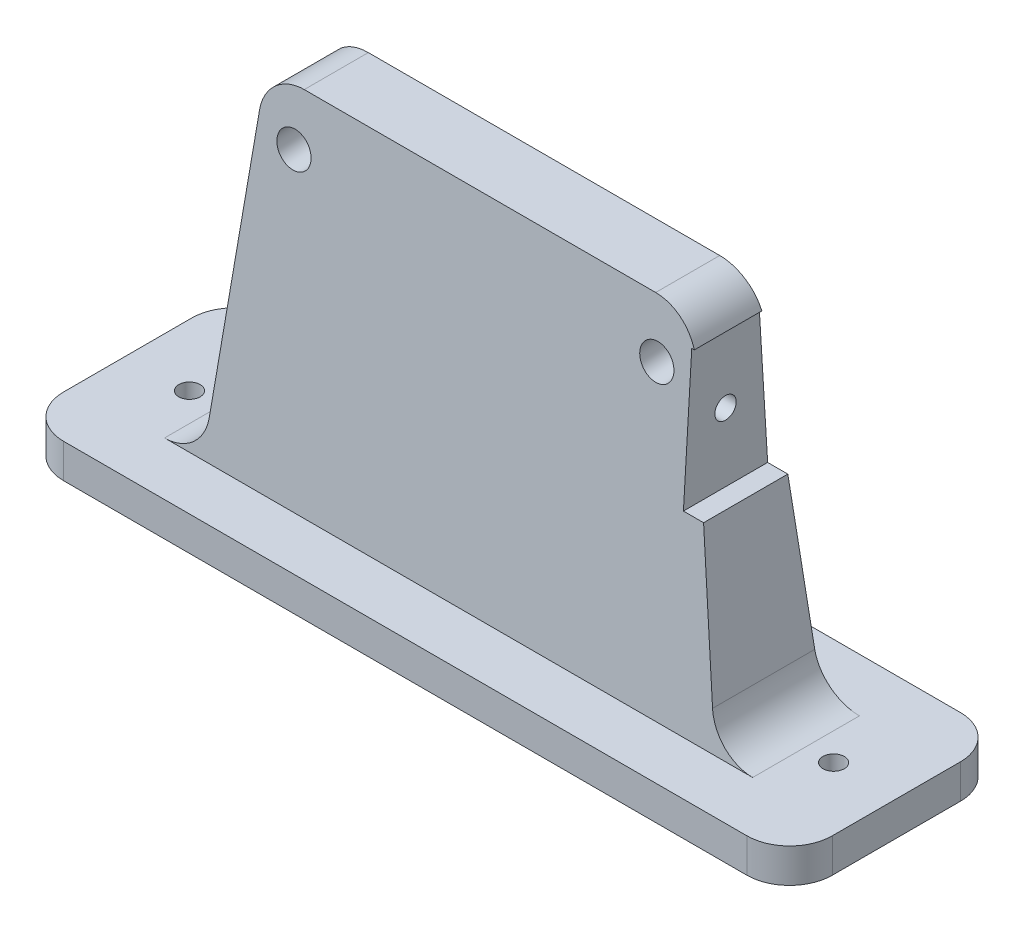
SolidWorks part; units mm, degrees
ref_plane "Front Plane" through (0, 0, 0) normal (0, 0, 1) x (1, 0, 0)
ref_plane "Top Plane" through (0, 0, 0) normal (0, 1, 0) x (1, 0, 0)
ref_plane "Right Plane" through (0, 0, 0) normal (1, 0, 0) x (0, 0, -1)
sketch "Sketch1" plane through (0, 0, 0) normal (0, 1, 0) x (1, 0, 0)
  line L1 (60, 25) -> (-60, 25)
  line L2 (60, 25) -> (60, -25)
  line L3 (60, -25) -> (-60, -25)
  line L4 (-60, 25) -> (-60, -25)
  line L5 (60, 25) -> (-60, -25) construction
  line L6 (60, -25) -> (-60, 25) construction
  point P0 (0, 0)
  dimension "D1" = 120
  dimension "D2" = 50
extrude "Boss-Extrude1" add sketch "Sketch1" along normal blind 8
ref_plane "Plane2" through (0, 90, 0) normal (0, 1, 0) x (1, 0, 0)
sketch "Sketch4" plane through (0, 90, 0) normal (0, 1, 0) x (1, 0, 0)
  line L1 (50, 7.5) -> (-50, 7.5)
  line L2 (50, 7.5) -> (50, -7.5)
  line L3 (50, -7.5) -> (-50, -7.5)
  line L4 (-50, 7.5) -> (-50, -7.5)
  line L5 (50, 7.5) -> (-50, -7.5) construction
  line L6 (50, -7.5) -> (-50, 7.5) construction
  point P0 (0, 0)
  dimension "D1" = 100
  dimension "D2" = 15
sketch "Sketch5" plane through (0, 8, 0) normal (0, 1, 0) x (1, 0, 0)
  line L0 (-60, 25) -> (-60, -25) construction
  line L1 (60, 12.5) -> (-60, 12.5)
  line L2 (60, 12.5) -> (60, -12.5)
  line L3 (60, -12.5) -> (-60, -12.5)
  line L4 (-60, 12.5) -> (-60, -12.5)
  line L5 (60, 12.5) -> (-60, -12.5) construction
  line L6 (60, -12.5) -> (-60, 12.5) construction
  point P0 (0, 0)
  dimension "D1" = 25
loft "Loft1" add profiles "Sketch5", "Sketch4" connector at (-60, 8, 12.5) connector at (-50, 90, 7.5)
sketch "Sketch6" plane through (0, 0.789, -12.9397) normal (0, 0.0609, -0.9981) x (-1, 0, 0)
  line L1 (-60, 7.2244) -> (60, 7.2244) construction
  circle A0 centre (-42.2142, 77.2244) radius 4
  circle A1 centre (42.7841, 77.7677) radius 4
  dimension "D1" = 8
  dimension "D2" = 8
  dimension "D3" = 85
  dimension "D4" = 70
extrude "Cut-Extrude1" cut sketch "Sketch6" against normal blind 82 contours A0
extrude "Cut-Extrude2" cut sketch "Sketch6<4>" against normal blind 82
sketch "Sketch6<4>" plane through (0, 0.789, -12.9397) normal (0, 0.0609, -0.9981) x (-1, 0, 0) same geometry as "Sketch6"
fillet "Fillet4" radius 10 1 edges type face fillet first side face at (0, 90, 0) second side face at (-57.5, 28.5, -5)
fillet "Fillet5" radius 10 1 edges type face fillet first side face at (4.4273, 90, 0) second side face at (57.5, 28.5, 5)
sketch "Sketch13" plane through (-60, 0, 0) normal (-1, 0, 0) x (0, 0, 1)
  line L1 (-25, 8) -> (25, 8)
  line L2 (-25, 8) -> (-25, 0)
  line L3 (-25, 0) -> (25, 0)
  line L4 (25, 8) -> (25, 0)
extrude "Boss-Extrude4" add sketch "Sketch13" along normal blind 30
fillet "Fillet6" radius 10 1 edges at (-90, 4, -25) type face fillet first side face at (-15, 4, -25) second side face at (-90, 4, 0)
fillet "Fillet7" radius 10 1 edges at (-90, 4, 25) type face fillet first side face at (-15, 4, 25) second side face at (-90, 4, 5)
sketch "Sketch14" plane through (60, 0, 0) normal (1, 0, 0) x (0, 0, -1)
  line L1 (-25, 8) -> (25, 8)
  line L2 (-25, 8) -> (-25, 0)
  line L3 (-25, 0) -> (25, 0)
  line L4 (25, 8) -> (25, 0)
extrude "Boss-Extrude5" add sketch "Sketch14" along normal blind 30
fillet "Fillet8" radius 10 1 edges at (90, 4, 25) type face fillet first side face at (90, 4, 0) second side face at (5, 4, 25)
fillet "Fillet9" radius 10 1 edges at (90, 4, -25) type face fillet first side face at (5, 4, -25) second side face at (90, 4, -5)
sketch "Sketch15" plane through (0, 8, 0) normal (0, 1, 0) x (1, 0, 0)
  circle A0 centre (75.3071, 0) radius 2.5
  circle A1 centre (-75.5235, 0) radius 2.5
extrude "Cut-Extrude3" cut sketch "Sketch15" against normal blind 10
sketch "Sketch16" plane through (0, 0, 0) normal (1, 0, 0) x (0, 0, -1)
  circle A0 centre (0, 52.8287) radius 2.5
  dimension "D1" = 5
ref_plane "Plane3" through (40, 0, 0) normal (1, 0, 0) x (0, 0, -1)
sketch "Sketch17" plane through (40, 0, 0) normal (1, 0, 0) x (0, 0, -1)
  line L0 (27.5, 90) -> (-27.5, 90) construction
  circle A0 centre (0, 67.28) radius 2.5
  dimension "D1" = 22.72
extrude "Cut-Extrude4" cut sketch "Sketch17" along normal blind 16 contours A0
sketch "Sketch18" plane through (0, 0.789, 12.9397) normal (0, 0.0609, 0.9981) x (1, 0, 0)
  line L0 (51.0719, 80.5709) -> (51.0719, 52.2775)
  line L1 (51.0719, 52.2775) -> (54.5159, 52.2775)
  line L2 (60, 7.2244) -> (51.0719, 80.5709) construction
  line L3 (54.5159, 52.2775) -> (51.0719, 80.5709)
  point P6 (51.0719, 52.2775)
extrude "Cut-Extrude5" cut sketch "Sketch18" against normal blind 20
sketch "Sketch19" plane through (60.0821, 7.3271, 0) normal (0.9926, 0.1211, 0) x (0, 0, -1)
  line L0 (-8.0359, 74.4308) -> (8.0359, 74.4308)
  line L1 (8.0359, 74.4308) -> (9.8367, 44.6802)
  line L2 (12.5, 0.6779) -> (8.0359, 74.4308) construction
  line L3 (9.8367, 44.6802) -> (-9.758, 45.9807)
  line L4 (-9.758, 45.9807) -> (-8.0359, 74.4308)
  line L5 (9.8367, 44.6802) -> (9.6457, 47.836)
  point P10 (0, 0)
  point P11 (8.0359, 74.4308)
extrude "Cut-Extrude6" cut sketch "Sketch19" along normal blind 1 and the other way blind 1 contours L4 L0 L1 L3
ref_plane "Plane4" through (50, 0, 0) normal (1, 0, 0) x (0, 0, -1)
sketch "Sketch21" plane through (50, 0, 0) normal (1, 0, 0) x (0, 0, -1)
  line L1 (10.3086, 83.28) -> (-10.3086, 83.28)
  line L2 (10.3086, 83.28) -> (10.3086, 51.28)
  line L3 (10.3086, 51.28) -> (-10.3086, 51.28)
  line L4 (-10.3086, 83.28) -> (-10.3086, 51.28)
  line L5 (10.3086, 83.28) -> (-10.3086, 51.28) construction
  line L6 (10.3086, 51.28) -> (-10.3086, 83.28) construction
  point P0 (0, 67.28)
extrude "Cut-Extrude7" cut sketch "Sketch21" along normal blind 5
fillet "Fillet11" radius 10 1 edges type face fillet first side face at (58.6805, 18.82, 3.125) second side face at (75.3071, 8, 2.5)
fillet "Fillet12" radius 10 1 edges type face fillet first side face at (-57.768, 26.3026, -3.125) second side face at (75.3071, 8, 2.5)
